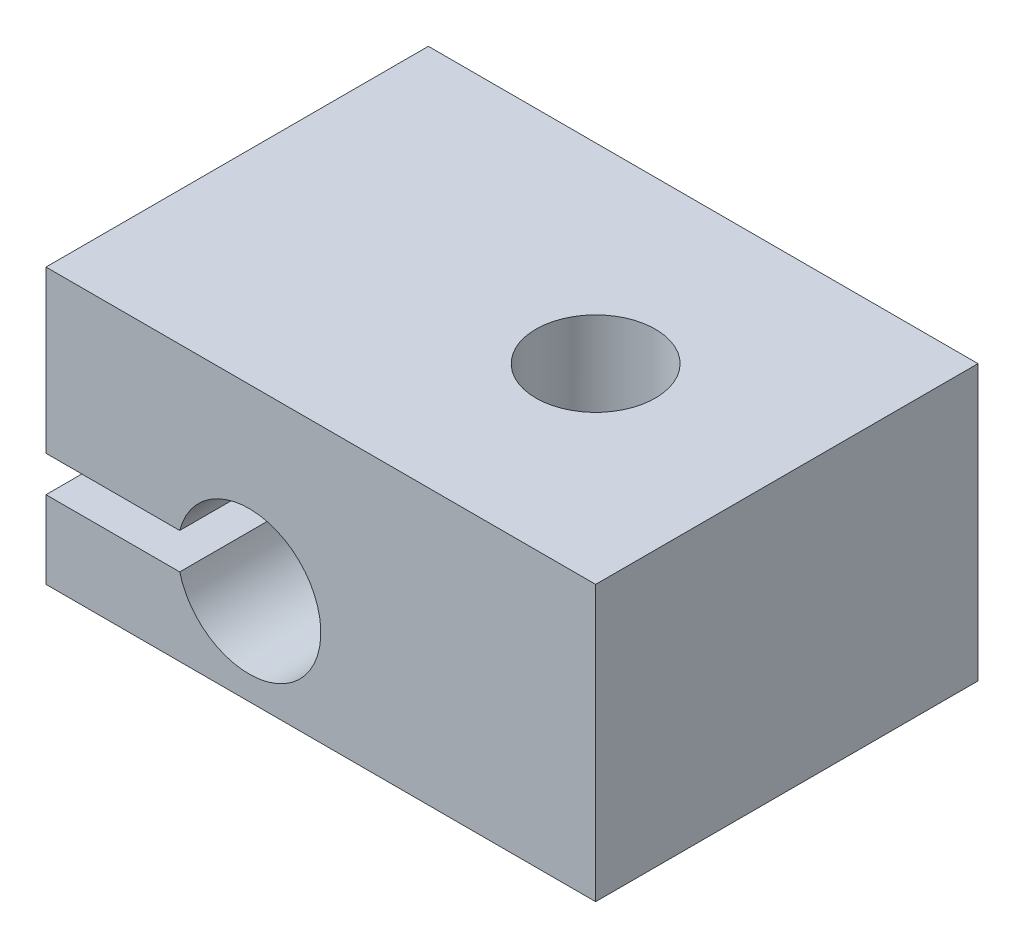
SolidWorks part; units mm, degrees
ref_plane "Front" through (0, 0, 0) normal (0, 0, 1) x (1, 0, 0)
ref_plane "Top" through (0, 0, 0) normal (0, 1, 0) x (1, 0, 0)
ref_plane "Right" through (0, 0, 0) normal (1, 0, 0) x (0, 0, -1)
sketch "Sketch1" plane through (0, 0, 0) normal (0, 1, 0) x (1, 0, 0)
  line L1 (0, 0) -> (23, 0)
  line L2 (0, 0) -> (0, 16)
  line L3 (0, 16) -> (23, 16)
  line L4 (23, 0) -> (23, 16)
  dimension "D1" = 23
  dimension "D2" = 16
extrude "Boss-Extrude1" add sketch "Sketch1" along normal blind 11.5
hole_wizard "M6x1.0 Tapped Hole1" positions "Sketch2" profile "Sketch3" tap size "M6x1.0" standard "ANSI Metric" end condition up to next
sketch "Sketch2" plane through (0, 11.5, 0) normal (0, 1, 0) x (1, 0, 0)
  line L0 (23, 8) -> (15, 8) construction
  line L1 (23, 0) -> (23, 16) construction
  point P0 (15, 8)
  dimension "D1" = 8
sketch "Sketch3" plane through (15, 11.5, -8) normal (1, 0, 0) x (0, 0, 1)
  line L0 (0, 0) -> (0, 11.5)
  line L1 (0, 11.5) -> (2.5, 11.5)
  line L2 (2.5, 11.5) -> (2.5, 0)
  line L5 (2.5, 0) -> (0, 0)
  line L11 (0, -6.35) -> (0, 107.95) construction
  dimension "Thru Tap Drill Dia." = 5
  dimension "Thru Tap Drill Depth" = 11.5
cosmetic thread "Hole Thread1" parameters "D2"=6
sketch "Sketch4" plane through (0, 0, 0) normal (0, 0, 1) x (1, 0, 0)
  line L0 (23, 11.5) -> (23, 0) construction
  line L1 (0, 0) -> (23, 0) construction
  line L2 (8.5, 4) -> (0, 4) construction
  line L3 (0, 11.5) -> (0, 0) construction
  line L4 (0, 4.75) -> (5.5953, 4.75)
  line L5 (0, 3.25) -> (5.5953, 3.25)
  circle A0 centre (8.5, 4) radius 3 construction
  arc A1 (5.5953, 4.75) -> (5.5953, 3.25) centre (8.5, 4) cw
  dimension "D3" = 6
  dimension "D1" = 14.5
  dimension "D2" = 4
  dimension "D4" = 0.75
  dimension "D5" = 0.75
extrude "Cut-Extrude1" cut sketch "Sketch4" against normal through all and the other way through all
equation "\"D5@Sketch4\"=\"D4@Sketch4\""
